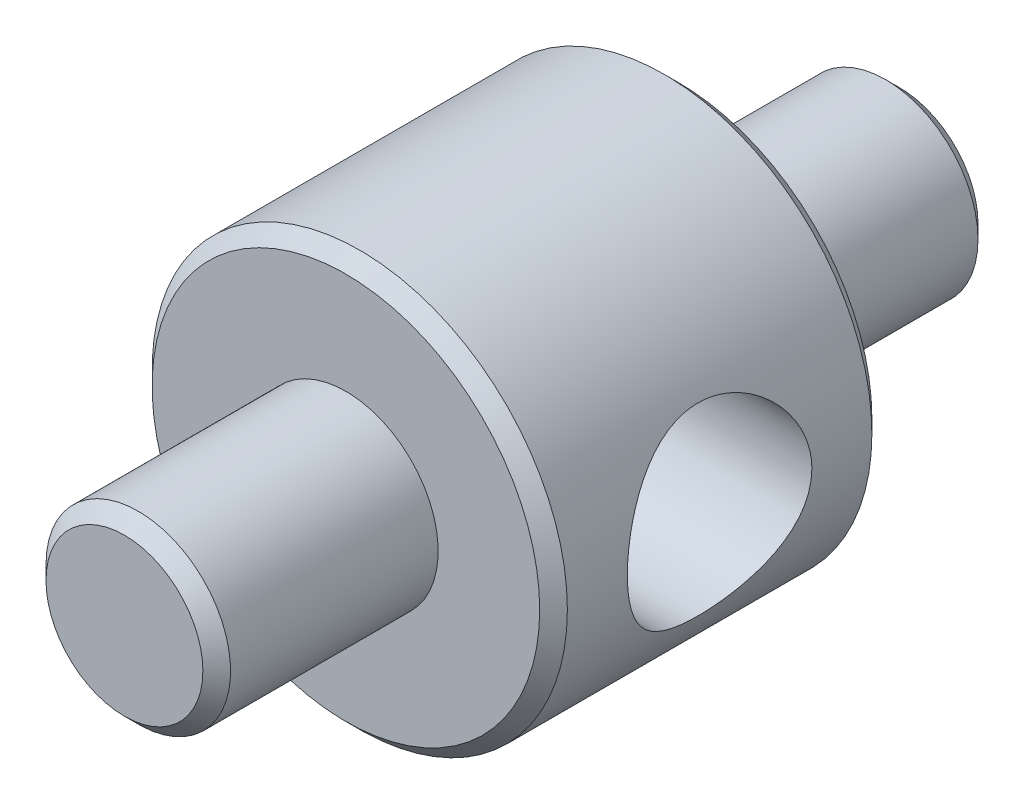
SolidWorks part; units mm, degrees
material "Gray Cast Iron"
ref_plane "Front Plane" through (0, 0, 0) normal (0, 0, 1) x (1, 0, 0)
ref_plane "Top Plane" through (0, 0, 0) normal (0, 1, 0) x (1, 0, 0)
ref_plane "Right Plane" through (0, 0, 0) normal (1, 0, 0) x (0, 0, -1)
sketch "Sketch1" plane through (0, 0, 0) normal (0, 0, 1) x (1, 0, 0)
  circle A0 centre (0, 0) radius 10
  circle A1 centre (0, 0) radius 22.5
  dimension "D1" = 20
  dimension "D2" = 45
extrude "Boss-Extrude1" add sketch "Sketch1" along normal mid plane 36 contours A0 | A1 A0 region at (0, 0, 0) region at (-21.8636, 0, 0)
extrude "Boss-Extrude2" add sketch "Sketch1<3>" along normal mid plane 84 contours A0 region at (0, 0, 0)
sketch "Sketch1<3>" plane through (0, 0, 0) normal (0, 0, 1) x (1, 0, 0) same geometry as "Sketch1"
sketch "Sketch2" plane through (0, 0, 0) normal (1, 0, 0) x (0, 0, -1)
  circle A0 centre (0, 0) radius 10
  dimension "D1" = 20
extrude "Cut-Extrude1" cut sketch "Sketch2" against normal through all both and the other way through all
chamfer "Chamfer1" distance 1.5 angle 45 4 edges at (10, 0, 42) (10, 0, -42) (22.5, 0, -18) (22.5, 0, 18)
